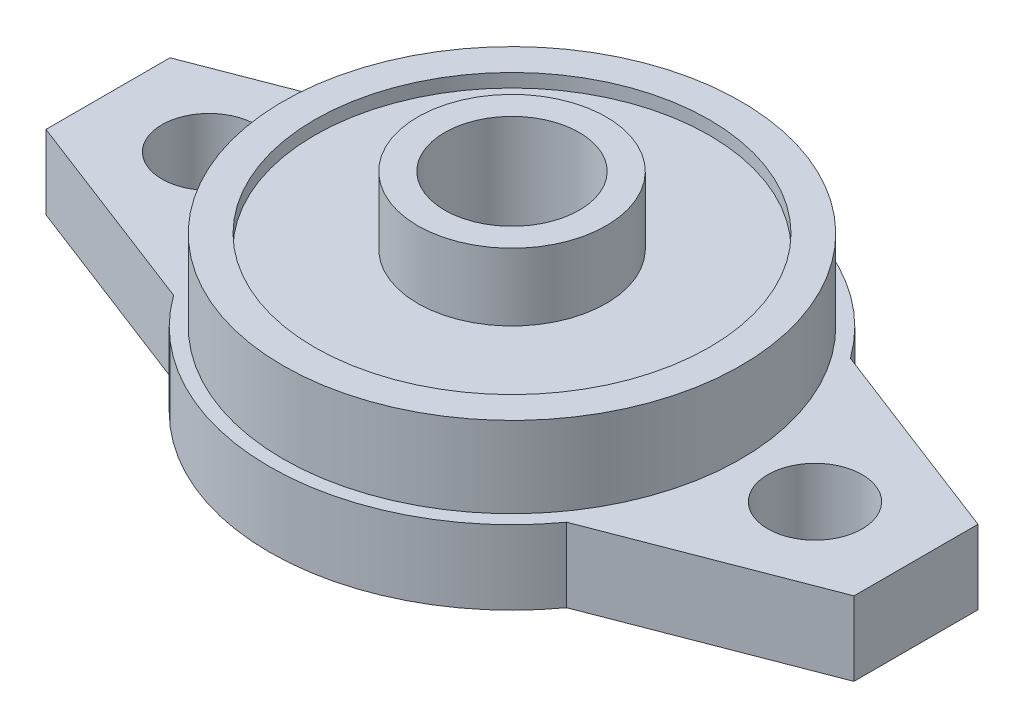
SolidWorks part; units mm, degrees
material "锌 AC41A 合金，作为铸件"
ref_plane "前视基准面" through (0, 0, 0) normal (0, 0, 1) x (1, 0, 0)
ref_plane "上视基准面" through (0, 0, 0) normal (0, 1, 0) x (1, 0, 0)
ref_plane "右视基准面" through (0, 0, 0) normal (1, 0, 0) x (0, 0, -1)
sketch "草图1" plane through (0, 0, 0) normal (0, 1, 0) x (1, 0, 0)
  line L0 (-643.3584, 0) -> (31524.5638, 0) construction
  line L1 (0, -643.3584) -> (0, 31524.5638) construction
  line L2 (-30, 4.605) -> (-30, -4.605)
  line L3 (-30, 4.605) -> (-14.5935, 10.5371)
  line L4 (-30, -4.605) -> (-14.5935, -10.5371)
  line L5 (30, -4.605) -> (14.5935, -10.5371)
  line L6 (30, 4.605) -> (14.5935, 10.5371)
  line L7 (30, 4.605) -> (30, -4.605)
  circle A0 centre (0, 0) radius 5
  circle A1 centre (0, 0) radius 18
  circle A2 centre (-22.5, 0) radius 3.5
  circle A3 centre (22.5, 0) radius 3.5
  point P13 (-30, 0)
  point P21 (30, 0)
  dimension "D1" = 7
  dimension "D2" = 36
  dimension "D3" = 10
  dimension "D4" = 30
  dimension "D5" = 22.5
extrude "凸台-拉伸1" add sketch "草图1" along normal blind 5.5 contours A1 L3 L2 L4 A2 | A1 A0 | A1 L5 L7 L6 A3 region at (-22.2029, 0, -7.3274) region at (0, 0, -17.4909) region at (22.2029, 0, -7.3274)
sketch "草图2" plane through (0, 5.5, 0) normal (0, 1, 0) x (1, 0, 0)
  circle A0 centre (0, 0) radius 17
  circle A1 centre (0, 0) radius 5 construction
  circle A2 centre (0, 0) radius 5
  dimension "D1" = 34
extrude "凸台-拉伸2" add sketch "草图2" along normal blind 6
sketch "草图3" plane through (0, 11.5, 0) normal (0, 1, 0) x (1, 0, 0)
  circle A0 centre (0, 0) radius 7
  circle A1 centre (0, 0) radius 5 construction
  circle A2 centre (0, 0) radius 5
  dimension "D1" = 14
extrude "凸台-拉伸3" add sketch "草图3" along normal blind 4
sketch "草图4" plane through (0, 11.5, 0) normal (0, 1, 0) x (1, 0, 0)
  circle A0 centre (0, 0) radius 7 construction
  circle A1 centre (0, 0) radius 7
  circle A2 centre (0, 0) radius 14.65
  circle A3 centre (0, 0) radius 17 construction
  dimension "D1" = 2.35
extrude "切除-拉伸1" cut sketch "草图4" against normal blind 1
